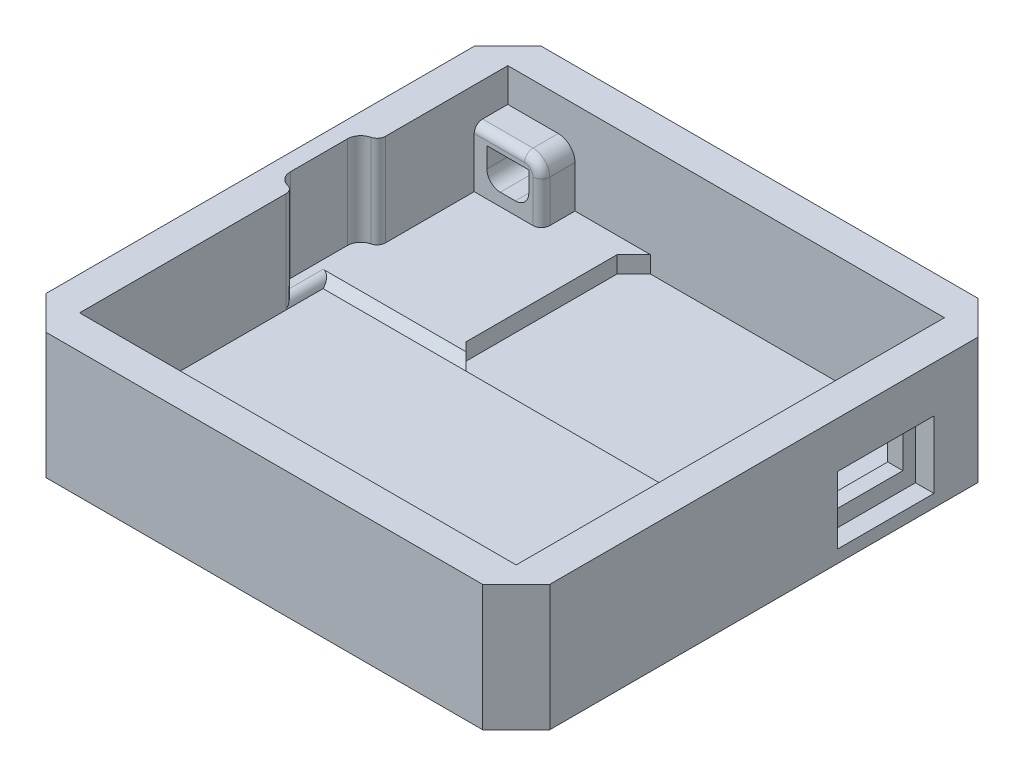
SolidWorks part; units mm, degrees
ref_plane "Front Plane" through (0, 0, 0) normal (0, 0, 1) x (1, 0, 0)
ref_plane "Top Plane" through (0, 0, 0) normal (0, 1, 0) x (1, 0, 0)
ref_plane "Right Plane" through (0, 0, 0) normal (1, 0, 0) x (0, 0, -1)
sketch "Sketch1" plane through (0, 0, 0) normal (0, 1, 0) x (1, 0, 0)
  line L1 (30, -29.5) -> (-30, -29.5)
  line L2 (30, -29.5) -> (30, 29.5)
  line L3 (30, 29.5) -> (-30, 29.5)
  line L4 (-30, -29.5) -> (-30, 29.5)
  line L5 (30, -29.5) -> (-30, 29.5) construction
  line L6 (30, 29.5) -> (-30, -29.5) construction
  point P0 (0, 0)
  dimension "D1" = 59
  dimension "D2" = 60
extrude "Boss-Extrude1" add sketch "Sketch1" along normal blind 4
sketch "Sketch2" plane through (0, 4, 0) normal (0, 1, 0) x (1, 0, 0)
  line L4 (-30, 29.5) -> (-30, -29.5)
  line L5 (-30, -29.5) -> (30, -29.5)
  line L6 (30, -29.5) -> (30, 29.5)
  line L7 (30, 29.5) -> (-30, 29.5)
  line L8 (-30, 29.5) -> (-30, -29.5)
  line L9 (-30, -29.5) -> (30, -29.5)
  line L10 (30, -29.5) -> (30, 29.5)
  line L11 (30, 29.5) -> (-30, 29.5)
  line L16 (-26, 25.5) -> (-26, -25.5)
  line L17 (-26, -25.5) -> (26, -25.5)
  line L18 (26, -25.5) -> (26, 25.5)
  line L19 (26, 25.5) -> (-26, 25.5)
  line L20 (-26, 25.5) -> (-26, -25.5)
  line L21 (-26, -25.5) -> (26, -25.5)
  line L22 (26, -25.5) -> (26, 25.5)
  line L23 (26, 25.5) -> (-26, 25.5)
  dimension "D1" = 0
  dimension "D2" = 4
extrude "Boss-Extrude2" add sketch "Sketch2" along normal blind 11 contours L22 L23 L20 L21
sketch "Sketch3" plane through (0, 4, 0) normal (0, 1, 0) x (1, 0, 0)
  line L0 (-9, 3.5) -> (-11, 5.5)
  line L1 (26, 25.5) -> (-9, 25.5)
  line L2 (26, 25.5) -> (26, 3.5)
  line L3 (26, 3.5) -> (-9, 3.5)
  line L4 (-11, 23.5) -> (-11, 5.5)
  line L5 (-9, 25.5) -> (-11, 23.5)
  point P1 (-11, 3.5)
  point P3 (-11, 25.5)
  dimension "D1" = 22
  dimension "D2" = 37
extrude "Cut-Extrude1" cut sketch "Sketch3" against normal blind 2
chamfer "Chamfer1" distance 4 angle 45 4 edges at (-30, 7.5, -29.5) (-30, 7.5, 29.5) (30, 7.5, 29.5) (30, 7.5, -29.5)
sketch "Sketch4" plane through (0, 4, 0) normal (0, 1, 0) x (1, 0, 0)
  line L1 (-26, 25.5) -> (-18, 25.5)
  line L2 (-26, 25.5) -> (-26, 21.5)
  line L3 (-26, 21.5) -> (-18, 21.5)
  line L4 (-18, 25.5) -> (-18, 21.5)
  dimension "D1" = 8
  dimension "D2" = 4
extrude "Boss-Extrude3" add sketch "Sketch4" along normal blind 7
sketch "Sketch5" plane through (0, 0, -21.5) normal (0, 0, 1) x (1, 0, 0)
  line L0 (-22, 11) -> (-22, 4) construction
  line L1 (-26, 11) -> (-18, 11) construction
  line L2 (-26, 4) -> (-18, 4) construction
  line L3 (-26, 7.5) -> (-18, 7.5) construction
  line L4 (-26, 11) -> (-26, 4) construction
  line L5 (-18, 11) -> (-18, 4) construction
  line L7 (-22.9, 5.5) -> (-21.1, 5.5)
  line L8 (-24.5, 7.1) -> (-24.5, 9.5)
  line L9 (-24.5, 9.5) -> (-19.5, 9.5)
  line L10 (-19.5, 7.1) -> (-19.5, 9.5)
  line L11 (-24.5, 5.5) -> (-19.5, 9.5) construction
  line L12 (-24.5, 9.5) -> (-19.5, 5.5) construction
  arc A0 (-19.5, 7.1) -> (-21.1, 5.5) centre (-21.1, 7.1) cw
  arc A1 (-24.5, 7.1) -> (-22.9, 5.5) centre (-22.9, 7.1) ccw
  point P12 (-22, 7.5)
  dimension "D3" = 1.6
  dimension "D4" = 1.6
  dimension "D1" = 5
  dimension "D2" = 4
extrude "Cut-Extrude2" cut sketch "Sketch5" against normal blind 6
sketch "Sketch6" plane through (0, 0, -27.5) normal (0, 0, 1) x (1, 0, 0)
  line L0 (-19.5, 9.5) -> (-24.5, 9.5) construction
  line L1 (-22.5, 9.5) -> (-21.5, 9.5)
  line L2 (-22.5, 9.5) -> (-22.5, 6.5)
  line L3 (-22.5, 6.5) -> (-21.5, 6.5)
  line L4 (-21.5, 9.5) -> (-21.5, 6.5)
  line L5 (-19.5, 7.1) -> (-19.5, 9.5) construction
  dimension "D1" = 3
  dimension "D2" = 1
  dimension "D3" = 2
extrude "Cut-Extrude3" cut sketch "Sketch6" against normal blind 6
fillet "Fillet1" radius 2 1 edges at (-18, 11, -23.5)
fillet "Fillet3" radius 1 3 edges at (-23, 11, -21.5) (-18.5858, 10.4142, -21.5) (-18, 6.5, -21.5)
sketch "Sketch7" plane through (0, 4, 0) normal (0, 1, 0) x (1, 0, 0)
  line L1 (26, 3.5) -> (-26, 3.5)
  line L2 (26, 3.5) -> (26, -25.5)
  line L3 (26, -25.5) -> (-26, -25.5)
  line L4 (-26, 3.5) -> (-26, -25.5)
extrude "Cut-Extrude4" cut sketch "Sketch7" against normal blind 1
chamfer "Chamfer2" distance 1 angle 45 1 edges at (-17.5, 4, -3.5)
sketch "Sketch8" plane through (0, 15, 0) normal (0, 1, 0) x (1, 0, 0)
  line L0 (-26, 25.5) -> (-26, -25.5) construction
  line L1 (-26, 0) -> (-26.4, 0)
  line L2 (-26, 0) -> (-26, 10)
  line L3 (-26, 10) -> (-26.4, 10)
  line L4 (-28, 1.6) -> (-28, 8.4)
  arc A0 (-28, 8.4) -> (-26.4, 10) centre (-26.4, 8.4) cw
  arc A1 (-28, 1.6) -> (-26.4, 0) centre (-26.4, 1.6) ccw
  point P8 (-28, 10)
  point P11 (-28, 0)
  dimension "D3" = 1.6
  dimension "D1" = 2
  dimension "D2" = 10
extrude "Cut-Extrude5" cut sketch "Sketch8" against normal blind 11
fillet "Fillet4" radius 1 1 edges at (-26, 4, -2.25)
fillet "Fillet5" radius 1 2 edges at (-26, 9.5, -10) (-26, 9, 0)
sketch "Sketch10" plane through (26, 0, 0) normal (-1, 0, 0) x (0, 0, 1)
  line L0 (-25.5, 15) -> (-25.5, 2) construction
  line L1 (-18.75, 3.5) -> (-10.25, 3.5)
  line L2 (-18.75, 3.5) -> (-18.75, 7.5)
  line L3 (-18.75, 7.5) -> (-10.25, 7.5)
  line L4 (-10.25, 3.5) -> (-10.25, 7.5)
  line L5 (-18.75, 3.5) -> (-10.25, 7.5) construction
  line L6 (-18.75, 7.5) -> (-10.25, 3.5) construction
  line L7 (-3.5, 2) -> (-25.5, 2) construction
  point P0 (-14.5, 5.5)
  dimension "D1" = 4
  dimension "D2" = 8.5
  dimension "D3" = 11
  dimension "D4" = 1.5
extrude "Cut-Extrude6" cut sketch "Sketch10" against normal blind 11
sketch "Sketch11" plane through (30, 0, 0) normal (1, 0, 0) x (0, 0, -1)
  line L1 (18.75, 7.5) -> (18.75, 3.5) construction
  line L2 (18.75, 5.5) -> (10.25, 5.5) construction
  line L3 (10.25, 3.5) -> (10.25, 7.5) construction
  line L4 (14.5, 3.5) -> (14.5, 7.5) construction
  line L5 (18.75, 3.5) -> (10.25, 3.5) construction
  line L6 (10.25, 7.5) -> (18.75, 7.5) construction
  line L8 (20.25, 9.5) -> (8.75, 9.5)
  line L9 (20.25, 9.5) -> (20.25, 1.5)
  line L10 (20.25, 1.5) -> (8.75, 1.5)
  line L11 (8.75, 9.5) -> (8.75, 1.5)
  line L12 (20.25, 9.5) -> (8.75, 1.5) construction
  line L13 (20.25, 1.5) -> (8.75, 9.5) construction
  point P12 (14.5, 5.5)
  dimension "D1" = 11.5
  dimension "D2" = 8
extrude "Cut-Extrude7" cut sketch "Sketch11" against normal blind 2.2
sketch "Sketch12" plane through (0, 0, -27.5) normal (0, 0, 1) x (1, 0, 0)
  line L1 (-24.5, 9.5) -> (-19.5, 9.5)
  line L2 (-24.5, 9.5) -> (-24.5, 7.1)
  line L3 (-24.5, 7.1) -> (-19.5, 7.1)
  line L4 (-19.5, 9.5) -> (-19.5, 7.1)
extrude "Cut-Extrude8" cut sketch "Sketch12" against normal blind 10
sketch "Sketch13" plane through (0, 0, -27.5) normal (0, 0, 1) x (1, 0, 0)
  line L6 (-22.5, 7.1) -> (-24.5, 7.1)
  line L7 (-22.9, 5.5) -> (-21.1, 5.5)
  line L8 (-19.5, 7.1) -> (-21.5, 7.1)
  line L9 (-21.5, 7.1) -> (-21.5, 6.5)
  line L10 (-21.5, 6.5) -> (-22.5, 6.5)
  line L11 (-22.5, 6.5) -> (-22.5, 7.1)
  line L12 (-22.5, 7.1) -> (-24.5, 7.1)
  line L13 (-22.9, 5.5) -> (-21.1, 5.5)
  line L14 (-19.5, 7.1) -> (-21.5, 7.1)
  line L15 (-21.5, 7.1) -> (-21.5, 6.5)
  line L16 (-21.5, 6.5) -> (-22.5, 6.5)
  line L17 (-22.5, 6.5) -> (-22.5, 7.1)
  arc A2 (-24.5, 7.1) -> (-22.9, 5.5) centre (-22.9, 7.1) ccw
  arc A3 (-21.1, 5.5) -> (-19.5, 7.1) centre (-21.1, 7.1) ccw
  arc A4 (-24.5, 7.1) -> (-22.9, 5.5) centre (-22.9, 7.1) ccw
  arc A5 (-21.1, 5.5) -> (-19.5, 7.1) centre (-21.1, 7.1) ccw
  dimension "D1" = 0
extrude "Cut-Extrude9" cut sketch "Sketch13" against normal blind 10
sketch "Sketch14" plane through (0, 0, -29.5) normal (0, 0, -1) x (-1, 0, 0)
  line L0 (19.5, 9.5) -> (24.5, 9.5) construction
  line L1 (20.7, 9.5) -> (20.9, 9.5)
  line L2 (20.7, 9.5) -> (20.7, 5.1051)
  line L3 (20.7, 5.1051) -> (20.9, 5.1051)
  line L4 (20.9, 9.5) -> (20.9, 5.1051)
  line L5 (19.5, 7.1) -> (19.5, 9.5) construction
  line L6 (21.9, 9.5) -> (22.1, 9.5)
  line L7 (21.9, 9.5) -> (21.9, 5.1051)
  line L8 (21.9, 5.1051) -> (22.1, 5.1051)
  line L9 (22.1, 9.5) -> (22.1, 5.1051)
  line L11 (23.1, 9.5) -> (23.3, 9.5)
  line L12 (23.1, 9.5) -> (23.1, 5.1051)
  line L13 (23.1, 5.1051) -> (23.3, 5.1051)
  line L14 (23.3, 9.5) -> (23.3, 5.1051)
  dimension "D1" = 0.2
  dimension "D2" = 0.2
  dimension "D3" = 1
  dimension "D4" = 1.2
  dimension "D5" = 0.2
  dimension "D6" = 1
extrude "Boss-Extrude4" add sketch "Sketch14" against normal blind 0.5
